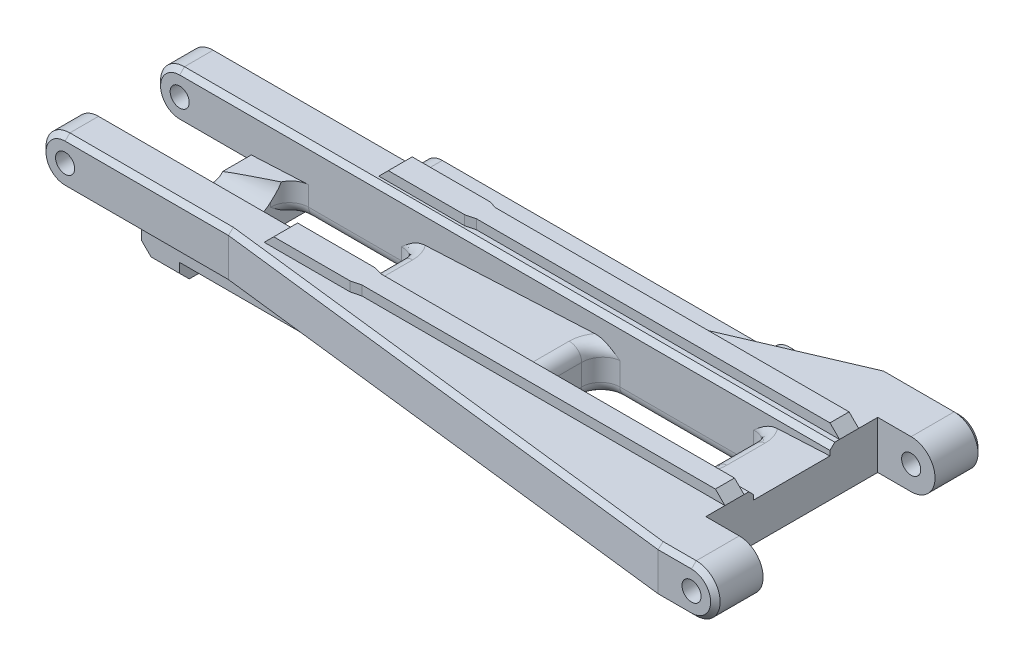
SolidWorks part; units mm, degrees
ref_plane "Front Plane" through (0, 0, 0) normal (0, 0, 1) x (1, 0, 0)
ref_plane "Top Plane" through (0, 0, 0) normal (0, 1, 0) x (1, 0, 0)
ref_plane "Right Plane" through (0, 0, 0) normal (1, 0, 0) x (0, 0, -1)
sketch "Sketch1" plane through (0, 0, 0) normal (0, 1, 0) x (1, 0, 0)
  line L0 (57.625, -22.225) -> (48.1, -22.225)
  line L1 (48.1, -22.225) -> (-32.8625, -12.7)
  line L2 (-32.8625, -12.7) -> (-63.975, -12.7)
  line L3 (-63.975, -12.7) -> (-63.975, -6.35)
  line L4 (-63.975, -6.35) -> (-48.1, -6.35)
  line L5 (48.1, -6.35) -> (48.1, -14.2875)
  line L6 (48.1, -14.2875) -> (57.625, -14.2875)
  line L7 (57.625, -14.2875) -> (57.625, -22.225)
  line L8 (-32.8625, 12.7) -> (19.525, 12.7)
  line L9 (48.1, -6.35) -> (48.1, 6.35)
  line L10 (-58.867, 0) -> (58.867, 0) construction
  line L11 (-48.1, -6.35) -> (-48.1, 6.35)
  line L12 (-48.1, 0) -> (48.1, 0)
  line L13 (57.625, 22.225) -> (41.75, 22.225)
  line L14 (57.625, 14.2875) -> (57.625, 22.225)
  line L15 (48.1, 14.2875) -> (57.625, 14.2875)
  line L16 (48.1, 6.35) -> (48.1, 14.2875)
  line L17 (-63.975, 6.35) -> (-48.1, 6.35)
  line L18 (-32.8625, 12.7) -> (-63.975, 12.7)
  line L19 (-63.975, 12.7) -> (-63.975, 6.35)
  line L20 (41.75, 22.225) -> (19.525, 12.7)
  line L21 (-32.8625, 12.7) -> (-32.8625, -12.7) construction
  dimension "D1" = 6.35
  dimension "D2" = 7.9375
  dimension "D3" = 7.9375
  dimension "D4" = 80.9625
  dimension "D5" = 9.525
  dimension "D6" = 9.525
  dimension "D7" = 31.1125
  dimension "D8" = 15.875
  dimension "D9" = 44.45
  dimension "D10" = 6.35
  dimension "D11" = 38.1
  dimension "D12" = 15.875
extrude "Boss-Extrude1" add sketch "Sketch1" against normal blind 3.9688 and the other way blind 3.9688 contours L12 L11 L4 L3 L2 L1 L0 L7 L6 L5 L9 | L13 L20 L8 L18 L19 L17 L11 L12 L9 L16 L15 L14 region at (3.6375, 0, 9.0931) region at (3.0041, 0, -8.204)
fillet "Fillet1" 2 edges at (-63.975, 3.9688, 9.525) (-63.975, -3.9688, 9.525) type full round first side face at (3.1945, 3.9688, 0) second side face at (3.1945, -3.9688, 0) middle face at (-63.975, 0, 9.525)
fillet "Fillet2" 2 edges at (-63.975, 3.9688, -9.525) (-63.975, -3.9688, -9.525) type full round first side face at (3.6906, 3.9688, 0) second side face at (3.6906, -3.9688, 0) middle face at (-63.975, 0, -9.525)
fillet "Fillet3" 2 edges at (57.625, 3.9688, 18.2562) (57.625, -3.9688, 18.2562) type full round first side face at (4.1867, 3.9688, 0) second side face at (4.1867, -3.9688, 0) middle face at (57.625, 0, 18.2562)
fillet "Fillet4" 2 edges at (57.625, 3.9688, -18.2562) (57.625, -3.9688, -18.2562) type full round first side face at (3.6906, 3.9688, 0) second side face at (3.6906, -3.9688, 0) middle face at (57.625, 0, -18.2562)
sketch "Sketch2" plane through (0, 0, 0) normal (0, 0, 1) x (1, 0, 0)
  line L0 (-48.1, 3.9688) -> (-48.1, -2.3813)
  line L1 (-48.1, -2.3813) -> (48.1, 2.3812)
  line L2 (48.1, 2.3812) -> (48.1, 3.9688)
  line L3 (48.1, 3.9688) -> (-48.1, 3.9688)
  line L4 (-32.8625, 3.9688) -> (-60.0062, 3.9688) construction
  line L5 (-32.8625, -3.9688) -> (-60.0062, -3.9688) construction
  line L6 (48.1, -3.9688) -> (-32.8625, -3.9688) construction
  dimension "D1" = 1.5875
  dimension "D2" = 6.35
extrude "Cut-Extrude1" cut sketch "Sketch2" against normal up to surface and the other way up to surface up to face at (-55.0453, 0, -6.35) other way up to face at (-55.0453, 0, 6.35)
sketch "Sketch3" plane through (0, 3.9688, 0) normal (0, 1, 0) x (1, 0, 0)
  line L0 (-48.1, 6.35) -> (48.1, 6.35) construction
  line L1 (35.4, 6.35) -> (13.175, 6.35)
  line L2 (38.575, 3.175) -> (38.575, -3.175)
  line L3 (35.4, -6.35) -> (13.175, -6.35)
  line L4 (10, 3.175) -> (10, -3.175)
  line L5 (48.1, -6.35) -> (-48.1, -6.35) construction
  line L6 (-60.0062, -6.35) -> (48.1, -6.35) construction
  line L7 (-23.1706, 6.35) -> (-38.575, 6.35)
  line L8 (-19.9956, 3.175) -> (-19.9956, -3.175)
  line L9 (-23.1706, -6.35) -> (-38.575, -6.35)
  line L10 (-41.75, 3.175) -> (-41.75, -3.175)
  line L11 (-48.1, 6.35) -> (-48.1, -6.35) construction
  line L12 (-60.0062, 6.35) -> (48.1, 6.35) construction
  line L13 (48.1, 6.35) -> (48.1, -6.35) construction
  arc A0 (38.575, -3.175) -> (35.4, -6.35) centre (35.4, -3.175) cw
  arc A1 (35.4, 6.35) -> (38.575, 3.175) centre (35.4, 3.175) cw
  arc A2 (13.175, -6.35) -> (10, -3.175) centre (13.175, -3.175) cw
  arc A3 (13.175, 6.35) -> (10, 3.175) centre (13.175, 3.175) ccw
  arc A4 (-23.1706, 6.35) -> (-19.9956, 3.175) centre (-23.1706, 3.175) cw
  arc A5 (-19.9956, -3.175) -> (-23.1706, -6.35) centre (-23.1706, -3.175) cw
  arc A6 (-38.575, -6.35) -> (-41.75, -3.175) centre (-38.575, -3.175) cw
  arc A7 (-38.575, 6.35) -> (-41.75, 3.175) centre (-38.575, 3.175) ccw
  point P24 (38.575, 6.35)
  point P27 (10, -6.35)
  point P30 (10, 6.35)
  point P33 (-19.9956, 6.35)
  point P38 (-41.75, -6.35)
  dimension "D5" = 3.175
  dimension "D1" = 28.575
  dimension "D2" = 29.9956
  dimension "D3" = 6.35
  dimension "D4" = 9.525
extrude "Cut-Extrude2" cut sketch "Sketch3" against normal through all
chamfer "Chamfer1" distance 0.7937 distance2 0.7937 22 edges at (50.8781, -3.9688, 22.225) (50.8781, 3.9688, 22.225) (57.625, 0, 22.225) (7.6188, 3.9688, 17.4625) (-46.4344, 3.9688, 12.7) (-63.975, 0, 12.7) (-46.4344, -3.9688, 12.7) (7.6188, -3.9688, 17.4625) (30.6375, -3.9688, -17.4625) (47.7031, -3.9688, -22.225) (-20.2406, -3.9688, -12.7) (57.625, 0, -22.225) (-63.975, 0, -12.7) (47.7031, 3.9688, -22.225) (30.6375, 3.9688, -17.4625) (-20.2406, 3.9688, -12.7) (-54.0531, -3.9688, -6.35) (-63.975, 0, -6.35) (-5.9531, 3.9688, -6.35) (-54.0531, -3.9688, 6.35) (-63.975, 0, 6.35) (-5.9531, 3.9688, 6.35)
sketch "Sketch4" plane through (0, 3.9688, 0) normal (0, 1, 0) x (1, 0, 0)
  line L0 (-12.225, 11.5094) -> (-28.1, 11.5094)
  line L1 (-28.1, 11.5094) -> (-28.1, 7.5406)
  line L2 (-28.1, 7.5406) -> (-12.225, 7.5406)
  line L3 (-12.225, 7.5406) -> (-12.225, 7.9375)
  line L4 (-12.225, 7.9375) -> (48.1, 7.9375)
  line L5 (48.1, 7.9375) -> (48.1, 11.1125)
  line L6 (48.1, 11.1125) -> (-12.225, 11.1125)
  line L7 (-12.225, 11.1125) -> (-12.225, 11.5094)
  line L8 (-28.1, 9.525) -> (48.1, 9.525) construction
  line L9 (41.75, 22.225) -> (53.6562, 22.225) construction
  line L10 (48.1, 14.2875) -> (48.1, 7.1438) construction
  line L11 (-45.9666, 0) -> (45.7701, 0) construction
  line L12 (-12.225, 7.9375) -> (-12.225, 7.5406)
  line L13 (48.1, 7.9375) -> (-12.225, 7.9375)
  line L14 (-12.225, 11.1125) -> (48.1, 11.1125)
  line L15 (-12.225, 11.5094) -> (-12.225, 11.1125)
  line L16 (-28.1, 11.5094) -> (-12.225, 11.5094)
  line L17 (-12.225, 7.5406) -> (-28.1, 7.5406)
  line L18 (-28.1, -9.525) -> (48.1, -9.525) construction
  line L19 (-12.225, -7.5406) -> (-28.1, -7.5406)
  line L20 (-28.1, -11.5094) -> (-12.225, -11.5094)
  line L21 (-12.225, -11.5094) -> (-12.225, -11.1125)
  line L22 (-12.225, -11.1125) -> (48.1, -11.1125)
  line L23 (48.1, -7.9375) -> (-12.225, -7.9375)
  line L24 (-12.225, -7.9375) -> (-12.225, -7.5406)
  line L25 (-12.225, -11.1125) -> (-12.225, -11.5094)
  line L26 (48.1, -11.1125) -> (-12.225, -11.1125)
  line L27 (48.1, -7.9375) -> (48.1, -11.1125)
  line L28 (-12.225, -7.9375) -> (48.1, -7.9375)
  line L29 (-12.225, -7.5406) -> (-12.225, -7.9375)
  line L30 (-28.1, -7.5406) -> (-12.225, -7.5406)
  line L31 (-28.1, -11.5094) -> (-28.1, -7.5406)
  line L32 (-12.225, -11.5094) -> (-28.1, -11.5094)
  line M7 (48.1, 7.1438) -> (48.1, 14.2875)
  dimension "D1" = 3.175
  dimension "D2" = 3.9688
  dimension "D3" = 14.2875
  dimension "D4" = 76.2
  dimension "D5" = 15.875
extrude "Boss-Extrude2" add sketch "Sketch4" along normal blind 1.5875 contours L6 L7 L0 L1 L2 L3 L4 M7 | L31 L20 L21 L22 L27 L23 L24 L19 region at (8.5068, 3.9688, -9.525) region at (8.5068, 3.9688, 9.525)
chamfer "Chamfer2" distance 1.5875 distance2 1.5875 4 edges at (48.1, 5.5563, 9.525) (48.1, 5.5563, -9.525) (-28.1, 5.5563, -9.525) (-28.1, 5.5563, 9.525)
chamfer "Chamfer3" distance 1.5875 distance2 0.3969 2 edges at (-12.225, 4.7625, -7.5406) (-12.225, 4.7625, 11.5094) first distance on face at (-19.7656, 4.7625, -7.5406) first distance on face at (-19.7656, 4.7625, 11.5094)
chamfer "Chamfer4" distance 0.3969 distance2 1.4111 2 edges at (-12.225, 4.7625, 7.5406) (-12.225, 4.7625, -11.5094) first distance on face at (-12.225, 4.7625, 7.7391) first distance on face at (-12.225, 4.7625, -11.3109)
sketch "Sketch5" plane through (0, -3.9688, 0) normal (0, -1, 0) x (1, 0, 0)
  line L0 (48.1, -14.2875) -> (48.1, 14.2875) construction
  line L1 (48.1, 11.9062) -> (-48.1, 11.9062)
  line L2 (48.1, 11.9062) -> (48.1, -11.9062)
  line L3 (48.1, -11.9062) -> (-48.1, -11.9062)
  line L4 (-48.1, 11.9062) -> (-48.1, -11.9062)
  line L5 (-48.1, 7.1438) -> (-48.1, -7.1438) construction
  line L6 (0, 0) -> (48.1, 0) construction
  line L7 (-38.575, 6.35) -> (-23.1706, 6.35) construction
  line L8 (-41.75, -3.175) -> (-41.75, 3.175) construction
  line L9 (-23.1706, -6.35) -> (-38.575, -6.35) construction
  line L10 (-19.9956, 3.175) -> (-19.9956, -3.175) construction
  line L11 (13.175, 6.35) -> (35.4, 6.35) construction
  line L12 (10, -3.175) -> (10, 3.175) construction
  line L13 (35.4, -6.35) -> (13.175, -6.35) construction
  line L14 (38.575, 3.175) -> (38.575, -3.175) construction
  line L15 (-38.575, 6.35) -> (-23.1706, 6.35)
  line L16 (-41.75, -3.175) -> (-41.75, 3.175)
  line L17 (-23.1706, -6.35) -> (-38.575, -6.35)
  line L18 (-19.9956, 3.175) -> (-19.9956, -3.175)
  line L19 (13.175, 6.35) -> (35.4, 6.35)
  line L20 (10, -3.175) -> (10, 3.175)
  line L21 (35.4, -6.35) -> (13.175, -6.35)
  line L22 (38.575, 3.175) -> (38.575, -3.175)
  arc A0 (-38.575, 6.35) -> (-41.75, 3.175) centre (-38.575, 3.175) ccw construction
  arc A1 (-41.75, -3.175) -> (-38.575, -6.35) centre (-38.575, -3.175) ccw construction
  arc A2 (-23.1706, -6.35) -> (-19.9956, -3.175) centre (-23.1706, -3.175) ccw construction
  arc A3 (-19.9956, 3.175) -> (-23.1706, 6.35) centre (-23.1706, 3.175) ccw construction
  arc A4 (13.175, 6.35) -> (10, 3.175) centre (13.175, 3.175) ccw construction
  arc A5 (10, -3.175) -> (13.175, -6.35) centre (13.175, -3.175) ccw construction
  arc A6 (35.4, -6.35) -> (38.575, -3.175) centre (35.4, -3.175) ccw construction
  arc A7 (38.575, 3.175) -> (35.4, 6.35) centre (35.4, 3.175) ccw construction
  arc A8 (-38.575, 6.35) -> (-41.75, 3.175) centre (-38.575, 3.175) ccw
  arc A9 (-41.75, -3.175) -> (-38.575, -6.35) centre (-38.575, -3.175) ccw
  arc A10 (-23.1706, -6.35) -> (-19.9956, -3.175) centre (-23.1706, -3.175) ccw
  arc A11 (-19.9956, 3.175) -> (-23.1706, 6.35) centre (-23.1706, 3.175) ccw
  arc A12 (13.175, 6.35) -> (10, 3.175) centre (13.175, 3.175) ccw
  arc A13 (10, -3.175) -> (13.175, -6.35) centre (13.175, -3.175) ccw
  arc A14 (35.4, -6.35) -> (38.575, -3.175) centre (35.4, -3.175) ccw
  arc A15 (38.575, 3.175) -> (35.4, 6.35) centre (35.4, 3.175) ccw
  dimension "D1" = 23.8125
extrude "Boss-Extrude3" add sketch "Sketch5" along normal blind 3.175
sketch "Sketch6" plane through (0, -7.1437, 0) normal (0, -1, 0) x (1, 0, 0)
  line L0 (-48.1, -11.9062) -> (48.1, -11.9062) construction
  line L1 (-48.1, 11.9062) -> (-41.75, 11.9062)
  line L2 (-48.1, 11.9062) -> (-48.1, -11.9062)
  line L3 (-48.1, -11.9062) -> (-41.75, -11.9062)
  line L4 (-41.75, 11.9062) -> (-41.75, -11.9062)
  line L5 (-41.75, 3.175) -> (-41.75, -3.175) construction
extrude "Boss-Extrude4" add sketch "Sketch6" along normal blind 1.5875
chamfer "Chamfer5" distance 3.175 angle 45 2 edges at (48.1, -7.1437, 0) (-48.1, -8.7312, 0) tangent propagation no
chamfer "Chamfer6" distance 1.5875 angle 45 2 edges at (-43.3375, -8.7312, 11.9062) (-43.3375, -8.7312, -11.9062) tangent propagation no
chamfer "Chamfer7" distance 1.5875 angle 45 2 edges
ref_plane "Plane1" through (0, 0, -15.875) normal (0, 0, -1) x (-1, 0, 0)
sketch "Sketch7" plane through (0, 0, -15.875) normal (0, 0, -1) x (-1, 0, 0)
  line L0 (-19.525, 3.175) -> (-41.75, 3.175) construction
  line L1 (29.05, 3.175) -> (-26.9333, 3.175)
  line L2 (29.05, 3.175) -> (29.05, -3.175)
  line L3 (29.05, -3.175) -> (-26.9333, -3.175)
  line L4 (-26.9333, 3.175) -> (-26.9333, -3.175)
  line L6 (-41.75, -3.175) -> (-19.525, -3.175) construction
  arc A0 (60.0062, -3.9688) -> (60.0062, 3.9688) centre (60.0062, 0) ccw construction
  point P9 (63.975, 0)
  dimension "D1" = 6.35
  dimension "D2" = 34.925
extrude "Boss-Extrude5" add sketch "Sketch7" against normal up to surface (3.175 mm away) up to face at (-21.0344, 0, -12.7)
fillet "Fillet5" 2 edges at (-29.05, 3.175, -14.2875) (-29.05, -3.175, -14.2875) type full round first side face at (-2.9104, 3.175, -14.2875) second side face at (-2.9104, -3.175, -14.2875) middle face at (-29.05, 0, -14.2875)
sketch "Sketch8" plane through (-48.1, 0, 0) normal (-1, 0, 0) x (0, 0, 1)
  line L0 (-6.35, -2.3813) -> (6.35, -2.3813) construction
  line L1 (0, 0) -> (0, -1.1906) construction
  line L2 (-6.35, -2.3813) -> (-6.35, -3.175) construction
  circle A0 centre (0, -1.1906) radius 1.9844
  point P2 (-1.5875, -2.3813)
  point P3 (1.5875, -2.3813)
  point P11 (0, -3.175)
  point P12 (0, -2.3813)
  dimension "D1" = 4.7625
  dimension "D2" = 0.7937
extrude "Cut-Extrude3" cut sketch "Sketch8" against normal blind 7.9375 draft 22 draft outward yes
sketch "Sketch9" plane through (0, 0, -15.875) normal (0, 0, -1) x (-1, 0, 0)
  line L0 (-26.9333, 3.175) -> (-41.75, 3.175) construction
  line L1 (-41.75, -3.175) -> (-26.9333, -3.175) construction
  circle A0 centre (-29.8437, 0) radius 3.175
  arc A2 (-53.6562, 3.9688) -> (-53.6562, -3.9688) centre (-53.6562, 0) ccw construction
  point P13 (-57.625, 0)
  dimension "D1" = 27.7812
extrude "Boss-Extrude6" add sketch "Sketch9" along normal blind 2.3813
chamfer "Chamfer8" distance 0.3969 1 edges at (26.6687, 0, -18.2563)
sketch "Sketch10" plane through (0, 0, -18.2562) normal (0, 0, -1) x (-1, 0, 0)
  circle A0 centre (-29.8438, 0) radius 1.5875
  circle A1 centre (-17.1438, 0) radius 1.5875
  circle A2 centre (0, 0) radius 1.5875
  circle A3 centre (7.1437, 0) radius 1.5875
  circle A4 centre (10.7156, 0) radius 1.5875
  circle A5 centre (14.2875, 0) radius 1.5875
  dimension "D1" = 3.175
  dimension "D2" = 12.7
  dimension "D3" = 3.5719
  dimension "D4" = 3.5719
  dimension "D5" = 7.1437
extrude "Cut-Extrude4" cut sketch "Sketch10" against normal blind 9.525 contours A0 | A2 | A3 | A4 | A5 | A1 region at (29.8437, 0, -18.2563) region at (0, 0, -18.2562) region at (-7.1438, 0, -18.2562) region at (-10.7156, 0, -18.2562) region at (-14.2875, 0, -18.2562)
sketch "Sketch11" plane through (0, 0, 22.225) normal (0, 0, 1) x (1, 0, 0)
  circle A0 centre (-60.0063, 0) radius 1.5875
  circle A1 centre (53.6562, 0) radius 1.5875
  dimension "D1" = 3.175
extrude "Cut-Extrude5" cut sketch "Sketch11" against normal through all
fillet "Fillet6" radius 2 24 edges at (37.6451, 1.8637, -5.4201) (37.6451, 1.8637, 5.4201) (10.9299, -7.1437, 5.4201) (24.2875, -7.1437, 6.35) (37.6451, -7.1437, 5.4201) (38.575, -7.1437, 0) (37.6451, -7.1437, -5.4201) (24.2875, -7.1437, -6.35) (10.9299, -7.1437, -5.4201) (10.9299, 0.5411, 5.4201) (10.9299, 0.5411, -5.4201) (-30.8728, -7.1437, -6.35) (-20.9256, -7.1437, -5.4201) (-30.8728, -7.1437, 6.35) (-20.9256, -7.1437, 5.4201) (-20.9256, -1.0359, -5.4201) (-20.9256, -1.0359, 5.4201) (38.575, 1.9097, 0) (10, -7.1437, 0) (10, 0.4951, 0) (-19.9956, -7.1437, 0) (-19.9956, -0.9899, 0)
